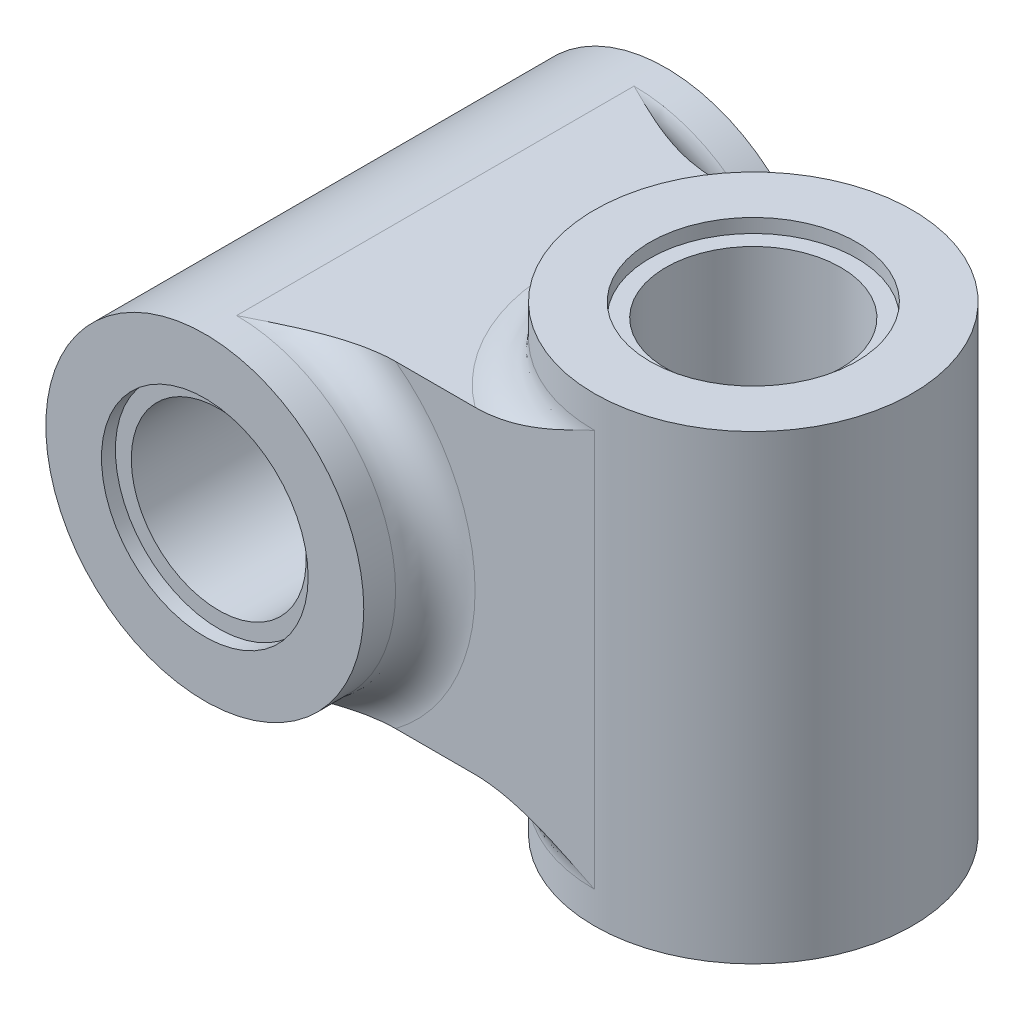
SolidWorks part; units mm, degrees
ref_plane "前视基准面" through (0, 0, 0) normal (0, 0, 1) x (1, 0, 0)
ref_plane "上视基准面" through (0, 0, 0) normal (0, 1, 0) x (1, 0, 0)
ref_plane "右视基准面" through (0, 0, 0) normal (1, 0, 0) x (0, 0, -1)
other "Configuration Table"
sketch "草图1" plane through (0, 0, 0) normal (0, 0, 1) x (1, 0, 0)
  circle A0 centre (0, 0) radius 20
  circle A1 centre (0, 0) radius 11
  dimension "D1" = 40
  dimension "D2" = 22
extrude "凸台-拉伸1" add sketch "草图1" along normal blind 58
sketch "草图2" plane through (0, 0, 0) normal (0, 1, 0) x (1, 0, 0)
  line L0 (-7.0354, -29) -> (29.939, -29) construction
  line L3 (20, 0) -> (-20, 0) construction
  line L4 (-20, -58) -> (20, -58) construction
  circle A2 centre (40, -29) radius 20
  circle A3 centre (40, -29) radius 11
  dimension "D1" = 40
  dimension "D2" = 22
  dimension "D3" = 40
extrude "凸台-拉伸2" add sketch "草图2" along normal mid plane 58 separate body contours A3 | A2 region at (40, 0, 29)
sketch "草图3" plane through (0, 0, 0) normal (1, 0, 0) x (0, 0, -1)
  line L0 (-58, -20) -> (0, -20) construction
  line L5 (-49, -20) -> (-9, -20)
  line L6 (-49, -20) -> (-49, 20)
  line L7 (-49, 20) -> (-9, 20)
  line L8 (-9, -20) -> (-9, 20)
  line L9 (0, 20) -> (-58, 20) construction
  line L10 (-9, -29) -> (-9, 29) construction
  line L11 (-49, 29) -> (-49, -29) construction
extrude "凸台-拉伸3" add sketch "草图3" along normal blind 40 contours L7 L8 L5 L6
sketch "草图5" plane through (0, 29, 0) normal (0, 1, 0) x (1, 0, 0)
  circle A0 centre (40, -29) radius 11 construction
  circle A1 centre (40, -29) radius 11
extrude "切除-拉伸1" cut sketch "草图5" against normal blind 118
sketch "草图6" plane through (0, 0, 0) normal (0, 0, -1) x (-1, 0, 0)
  circle A0 centre (0, 0) radius 11 construction
  circle A1 centre (0, 0) radius 11
extrude "切除-拉伸2" cut sketch "草图6" against normal blind 118
fillet "圆角1" radius 5 4 edges at (20, -20, 29) (20, 0, 9) (20, 20, 29) (20, 0, 49)
sketch "草图7" plane through (0, 0, 0) normal (0, 0, -1) x (-1, 0, 0)
  circle A0 centre (0, 0) radius 13
  dimension "D1" = 26
extrude "切除-拉伸3" cut sketch "草图7" against normal blind 1.75
sketch "草图8" plane through (0, 0, 58) normal (0, 0, 1) x (1, 0, 0)
  circle A0 centre (0, 0) radius 13
  dimension "D1" = 26
extrude "切除-拉伸4" cut sketch "草图8" against normal blind 1.75
sketch "草图9" plane through (0, 29, 0) normal (0, 1, 0) x (1, 0, 0)
  circle A0 centre (40, -29) radius 13
  dimension "D1" = 26
extrude "切除-拉伸5" cut sketch "草图9" against normal blind 1.75
sketch "草图10" plane through (0, -29, 0) normal (0, -1, 0) x (1, 0, 0)
  circle A0 centre (40, 29) radius 13
  dimension "D1" = 26
extrude "切除-拉伸6" cut sketch "草图10" against normal blind 1.75
